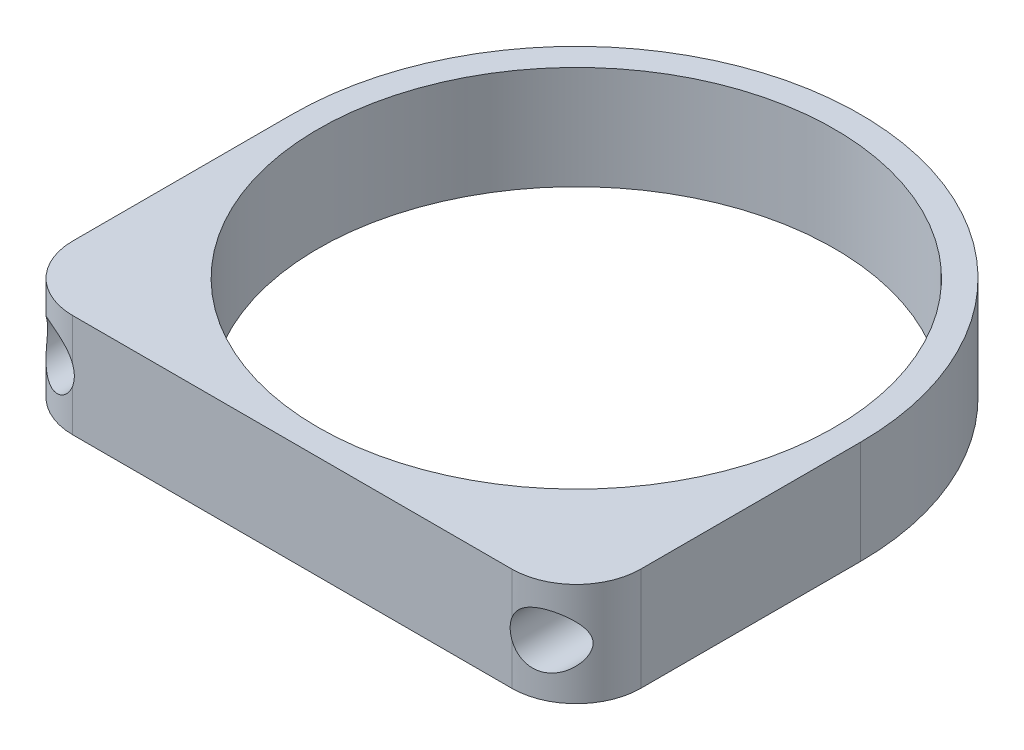
SolidWorks part; units mm, degrees
ref_plane "Front Plane" through (0, 0, 0) normal (0, 0, 1) x (1, 0, 0)
ref_plane "Top Plane" through (0, 0, 0) normal (0, 1, 0) x (1, 0, 0)
ref_plane "Right Plane" through (0, 0, 0) normal (1, 0, 0) x (0, 0, -1)
sketch "Sketch1" plane through (0, 0, 0) normal (0, 1, 0) x (1, 0, 0)
  line L0 (-44, 0) -> (-44, -44)
  line L1 (-44, -44) -> (44, -44)
  line L2 (44, -44) -> (44, 0)
  arc A0 (44, 0) -> (-44, 0) centre (0, 0) ccw
  dimension "D1" = 88
extrude "Boss-Extrude1" add sketch "Sketch1" along normal blind 16
sketch "Sketch2" plane through (0, 0, 44) normal (0, 0, 1) x (1, 0, 0)
  line L0 (-44, 16) -> (-44, 0) construction
  line L1 (-1044, 8) -> (48956, 8) construction
  line L2 (0, -1000) -> (0, 49000) construction
  circle A0 centre (-38, 8) radius 4.25
  circle A1 centre (38, 8) radius 4.25
  point P7 (-44, 8)
  dimension "D1" = 8.5
  dimension "D2" = 6
extrude "Cut-Extrude1" cut sketch "Sketch2" against normal blind 20
fillet "Fillet1" radius 10 2 edges at (44, 8, 44) (-44, 8, 44)
sketch "Sketch3" plane through (0, 16, 0) normal (0, 1, 0) x (1, 0, 0)
  circle A0 centre (0, 0) radius 40
  dimension "D1" = 80
extrude "Cut-Extrude2" cut sketch "Sketch3" against normal through all
